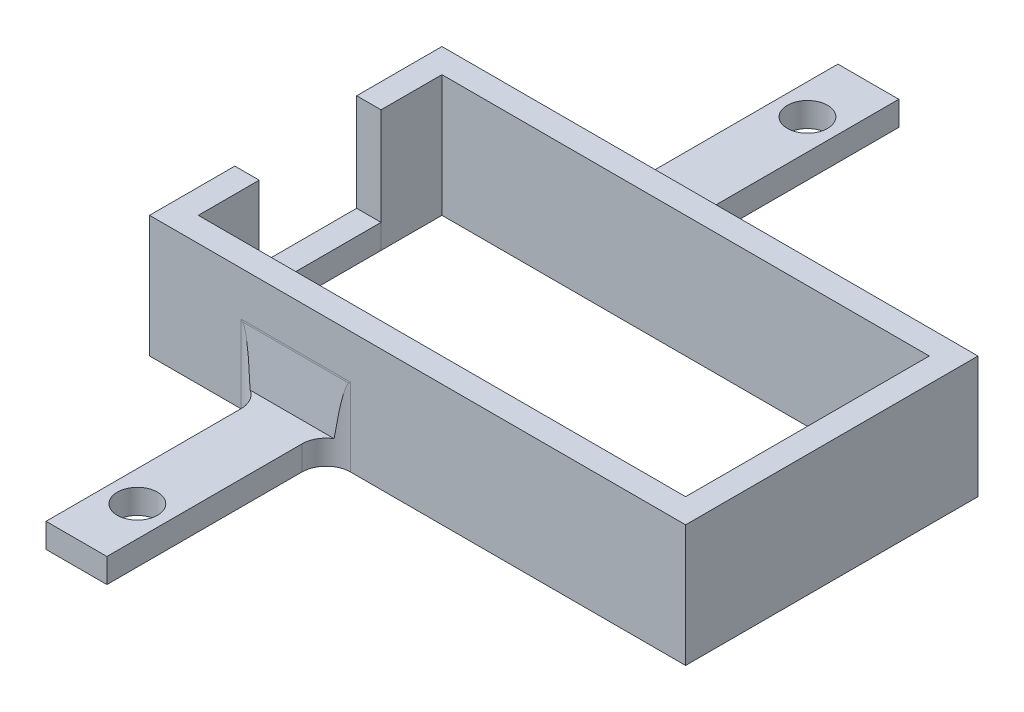
SolidWorks part; units mm, degrees
ref_plane "Plan de face" through (0, 0, 0) normal (0, 0, 1) x (1, 0, 0)
ref_plane "Plan de dessus" through (0, 0, 0) normal (0, 1, 0) x (1, 0, 0)
ref_plane "Plan de droite" through (0, 0, 0) normal (1, 0, 0) x (0, 0, -1)
sketch "Esquisse1" plane through (0, 0, 0) normal (0, 1, 0) x (1, 0, 0)
  line L0 (2.5, 60) -> (2.5, 5) construction
  line L1 (0, 0) -> (5, 0)
  line L2 (0, 0) -> (0, 65)
  line L3 (0, 65) -> (5, 65)
  line L4 (5, 0) -> (5, 65)
  line L5 (-1.505, 30) -> (9.8654, 30) construction
  line L6 (-7.5, 40) -> (32.5, 40)
  line L7 (-7.5, 40) -> (-7.5, 20)
  line L8 (-7.5, 20) -> (32.5, 20)
  line L9 (32.5, 40) -> (32.5, 20)
  line L10 (-9.5, 42) -> (34.5, 42)
  line L11 (-9.5, 42) -> (-9.5, 18)
  line L12 (-9.5, 18) -> (34.5, 18)
  line L13 (34.5, 42) -> (34.5, 18)
  line L15 (-9.5, 35) -> (-7.5, 35)
  line L16 (-9.5, 35) -> (-9.5, 25)
  line L17 (-9.5, 25) -> (-7.5, 25)
  line L18 (-7.5, 35) -> (-7.5, 25)
  circle A0 centre (2.5, 60) radius 1.65
  circle A1 centre (2.5, 5) radius 1.65
  point P18 (2.5, 65)
  dimension "D1" = 3.3
  dimension "D2" = 3.3
  dimension "D3" = 55
  dimension "D4" = 5
  dimension "D5" = 5
  dimension "D6" = 20
  dimension "D7" = 40
  dimension "D8" = 2
  dimension "D9" = 2
  dimension "D10" = 44
  dimension "D11" = 24
  dimension "D12" = 5
  dimension "D13" = 10
  dimension "D14" = 25
  dimension "D15" = 10
  dimension "D16" = 10
  dimension "D17" = 7
extrude "Boss.-Extru.1" add sketch "Esquisse1" along normal blind 10 contours L2 L10 L4 L3 A0 | L10 L2 L6 L4 | L11 L15 L7 L6 L2 L10 | L13 L10 L4 L6 L9 L8 L12 | L2 L12 L4 L8 | L12 L2 L1 L4 A1 | L17 L11 L12 L2 L8 L7 region at (2.5, 0, -9.4201) region at (-4.75, 0, -18.118) region at (2.5, 0, -19) region at (5.3803, 0, -19) region at (-3.75, 0, -40.118) region at (2.5, 0, -41) region at (2.5, 0, -52.9777)
sketch "Esquisse2" plane through (0, 10, 0) normal (0, 1, 0) x (1, 0, 0)
  line L1 (0, 18) -> (5, 18)
  line L2 (0, 18) -> (0, 0)
  line L3 (0, 0) -> (5, 0)
  line L4 (5, 18) -> (5, 0)
  line L5 (0, 65) -> (5, 65)
  line L6 (0, 65) -> (0, 42)
  line L7 (0, 42) -> (5, 42)
  line L8 (5, 65) -> (5, 42)
extrude "Enlèv. mat.-Extru.1" cut sketch "Esquisse2" against normal blind 8
sketch "Esquisse3" plane through (5, 0, 0) normal (1, 0, 0) x (0, 0, -1)
  line L0 (17.7013, 2) -> (18, 6.3153)
  line L1 (0, 2) -> (18, 2) construction
  line L2 (18, 10) -> (18, 0) construction
  line L3 (18, 6.3153) -> (18, 2)
  line L4 (18, 2) -> (17.7013, 2)
  line L5 (42, 6.3153) -> (42, 2)
  line L6 (42, 10) -> (42, 0) construction
  line L7 (42, 2) -> (42.2987, 2)
  line L8 (42, 2) -> (65, 2) construction
  line L9 (42.2987, 2) -> (42, 6.3153)
  point P13 (24.18, 6.3153)
extrude "Boss.-Extru.2" add sketch "Esquisse3" against normal blind 5
fillet "Congé1" radius 2 6 edges at (2.5, 6.3153, -42) (2.5, 6.3153, -18) (0, 3.1577, -42) (5, 3.1577, -42) (0, 3.1577, -18) (5, 3.1577, -18)
sketch "Esquisse5" plane through (0, 0, 0) normal (0, -1, 0) x (1, 0, 0)
  line L5 (-9.5, -25) -> (-7.5, -25)
  line L6 (-9.5, -25) -> (-9.5, -35)
  line L7 (-9.5, -35) -> (-7.5, -35)
  line L8 (-7.5, -25) -> (-7.5, -35)
extrude "Boss.-Extru.3" add sketch "Esquisse5" against normal blind 2 separate body
